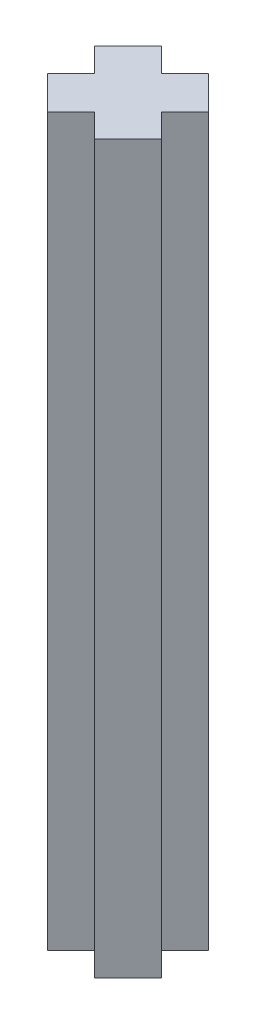
SolidWorks part; units mm, degrees
ref_plane "Front Plane" through (0, 0, 0) normal (0, 0, 1) x (1, 0, 0)
ref_plane "Top Plane" through (0, 0, 0) normal (0, 1, 0) x (1, 0, 0)
ref_plane "Right Plane" through (0, 0, 0) normal (1, 0, 0) x (0, 0, -1)
sketch "Sketch1" plane through (0, 0, 0) normal (0, 1, 0) x (1, 0, 0)
  line L0 (-0.627, 2.9162) -> (-2.423, 4.7122)
  line L1 (-3.167, -2.1638) -> (1.913, -2.1638) construction
  line L2 (-3.167, -2.1638) -> (-3.167, 2.9162) construction
  line L3 (-3.167, 2.9162) -> (1.913, 2.9162) construction
  line L4 (1.913, -2.1638) -> (1.913, 2.9162) construction
  line L5 (-3.167, -2.1638) -> (1.913, 2.9162) construction
  line L6 (-3.167, 2.9162) -> (1.913, -2.1638) construction
  line L7 (-3.167, 0.3762) -> (-4.963, 2.1722)
  line L8 (-4.963, 2.1722) -> (-2.423, 4.7122)
  line L9 (1.913, 0.3762) -> (3.7091, -1.4199)
  line L10 (-0.627, -2.1638) -> (1.1691, -3.9599)
  line L11 (1.1691, -3.9599) -> (3.7091, -1.4199)
  line L12 (-3.167, 0.3762) -> (-4.963, -1.4199)
  line L13 (-0.627, -2.1638) -> (-2.423, -3.9599)
  line L14 (-4.963, -1.4199) -> (-2.423, -3.9599)
  line L15 (1.913, 0.3762) -> (3.7091, 2.1722)
  line L16 (1.1691, 4.7122) -> (3.7091, 2.1722)
  line L17 (-0.627, 2.9162) -> (1.1691, 4.7122)
  point P0 (-0.627, 0.3762)
  dimension "D1" = 2.54
  dimension "D2" = 5.08
  dimension "D3" = 5.08
  dimension "D4" = 8.6721
  dimension "D5" = 3.5921
  dimension "D6" = 3.5921
  dimension "D7" = 3.5921
  dimension "D8" = 3.5921
  dimension "D9" = 8.6721
  dimension "D10" = 0
  dimension "D11" = 3.5921
  dimension "D12" = 5.08
  dimension "D13" = 2.54
  dimension "D14" = 2.54
  dimension "D15" = 2.54
  dimension "D16" = 2.54
  dimension "D17" = 2.54
  dimension "D18" = 2.54
  dimension "D19" = 2.54
  dimension "D20" = 2.54
extrude "Boss-Extrude1" add sketch "Sketch1" along normal blind 55.2174
scale "Scale1" scale about centroid uniform scaling yes scale factor 0.92
